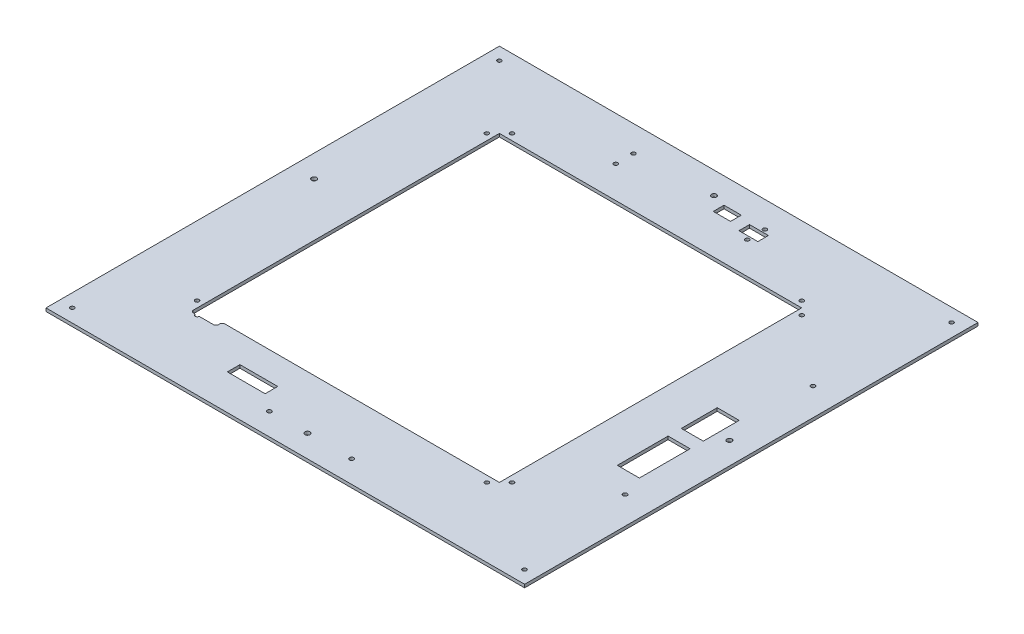
SolidWorks part; units mm, degrees
ref_plane "Front" through (0, 0, 0) normal (0, 0, 1) x (1, 0, 0)
ref_plane "Top" through (0, 0, 0) normal (0, 1, 0) x (1, 0, 0)
ref_plane "Right" through (0, 0, 0) normal (1, 0, 0) x (0, 0, -1)
sketch "Sketch1" plane through (0, 0, 0) normal (0, 1, 0) x (1, 0, 0)
  line L0 (-55, 0) -> (55, 0) construction
  line L1 (-242.5515, 228.6) -> (240.0485, 228.6)
  line L2 (-242.5515, 228.6) -> (-242.5515, -228.6)
  line L3 (-242.5515, -228.6) -> (240.0485, -228.6)
  line L4 (240.0485, 228.6) -> (240.0485, -228.6)
  line L5 (-242.5515, 228.6) -> (240.0485, -228.6) construction
  line L6 (-242.5515, -228.6) -> (240.0485, 228.6) construction
  line L7 (-166.3515, 152.4) -> (138.4485, 152.4)
  line L8 (-166.3515, 152.4) -> (-166.3515, -152.4)
  line L9 (-166.3515, -152.4) -> (138.4485, -152.4)
  line L10 (138.4485, 152.4) -> (138.4485, -152.4)
  line L11 (-166.3515, 152.4) -> (138.4485, -152.4) construction
  line L12 (-166.3515, -152.4) -> (138.4485, 152.4) construction
  line L13 (-160.0015, 146.05) -> (132.0985, 146.05)
  line L14 (-160.0015, 146.05) -> (-160.0015, -146.05)
  line L15 (-160.0015, -146.05) -> (132.0985, -146.05)
  line L16 (132.0985, 146.05) -> (132.0985, -146.05)
  line L17 (-160.0015, 146.05) -> (132.0985, -146.05) construction
  line L18 (-160.0015, -146.05) -> (132.0985, 146.05) construction
  line L19 (-166.3515, -152.4) -> (-140.9515, -152.4)
  line L20 (-166.3515, -152.4) -> (-166.3515, -158.75)
  line L21 (-166.3515, -158.75) -> (-140.9515, -158.75)
  line L22 (-140.9515, -152.4) -> (-140.9515, -158.75)
  line L23 (-242.5515, 0) -> (240.0485, 0) construction
  line L24 (58.4385, 188.214) -> (39.3885, 188.214)
  line L25 (58.4385, 188.214) -> (58.4385, 198.882)
  line L26 (58.4385, 198.882) -> (39.3885, 198.882)
  line L27 (39.3885, 188.214) -> (39.3885, 198.882)
  line L28 (182.9854, -26.8512) -> (205.1825, -26.8512)
  line L29 (182.9854, -26.8512) -> (182.9854, -78.0068)
  line L30 (182.9854, -78.0068) -> (205.1825, -78.0068)
  line L31 (205.1825, -26.8512) -> (205.1825, -78.0068)
  line L32 (182.9854, -13.5376) -> (205.1825, -13.5376)
  line L33 (182.9854, -13.5376) -> (182.9854, 22.6879)
  line L34 (182.9854, 22.6879) -> (205.1825, 22.6879)
  line L35 (205.1825, -13.5376) -> (205.1825, 22.6879)
  line L40 (27.0379, 202.954) -> (9.5991, 202.954)
  line L41 (27.0379, 202.954) -> (27.0379, 192.0704)
  line L42 (27.0379, 192.0704) -> (9.5991, 192.0704)
  line L43 (9.5991, 202.954) -> (9.5991, 192.0704)
  line L44 (-95.2315, -180.3456) -> (-57.1315, -180.3456)
  line L45 (-95.2315, -180.3456) -> (-95.2315, -193.0456)
  line L46 (-95.2315, -193.0456) -> (-57.1315, -193.0456)
  line L47 (-57.1315, -180.3456) -> (-57.1315, -193.0456)
  circle A0 centre (51.3519, 202.311) radius 2
  circle A1 centre (51.3519, 184.531) radius 2
  circle A2 centre (-81.1091, 202.311) radius 2
  circle A3 centre (-81.1091, 184.531) radius 2
  circle A4 centre (212.3904, -99.5798) radius 2.0955
  circle A5 centre (212.3904, 89.828) radius 2.0955
  circle A6 centre (-39.6436, -206.2861) radius 2.1
  circle A7 centre (43.3382, -206.2861) radius 2.1
  circle A8 centre (-172.7335, 146.082) radius 2
  circle A9 centre (-160.0335, 158.782) radius 2
  circle A12 centre (-160.0335, -158.782) radius 2
  circle A13 centre (-172.7335, -146.082) radius 2
  circle A14 centre (132.1305, 158.782) radius 2
  circle A15 centre (144.8305, 146.082) radius 2
  circle A16 centre (144.8305, -146.082) radius 2
  circle A17 centre (132.1305, -158.782) radius 2
  circle A18 centre (-229.8327, 215.8812) radius 2
  circle A19 centre (226.7201, 215.2716) radius 2
  circle A20 centre (-229.3755, -215.2716) radius 2
  circle A21 centre (227.2281, -215.9066) radius 2
  circle A22 centre (-220.0871, 19.264) radius 2.54
  circle A23 centre (-1.2915, -206.2372) radius 2.54
  circle A24 centre (-3.8315, 206.2626) radius 2.54
  circle A25 centre (217.7111, 0.294) radius 2.54
  point P0 (-1.2515, 0)
  point P6 (-44.5662, -1.1741)
  point P11 (-84.1987, 3.6789)
  point P21 (-13.9515, 0)
  point P22 (-13.9515, 0)
  point P23 (-1.2515, 0)
  dimension "D15" = 4
  dimension "D16" = 4
  dimension "D17" = 26.289
  dimension "D18" = 17.78
  dimension "D19" = 188.6966
  dimension "D20" = 132.461
  dimension "D22" = 27.6581
  dimension "D23" = 4.191
  dimension "D24" = 129.0202
  dimension "D26" = 4.2
  dimension "D27" = 22.3139
  dimension "D28" = 202.9079
  dimension "D29" = 82.9818
  dimension "D33" = 69.818
  dimension "D34" = 82.518
  dimension "D35" = 4
  dimension "D36" = 69.818
  dimension "D37" = 82.518
  dimension "D38" = 4
  dimension "D39" = 107.918
  dimension "D40" = 69.818
  dimension "D41" = 95.218
  dimension "D42" = 82.518
  dimension "D43" = 95.218
  dimension "D44" = 82.518
  dimension "D45" = 69.818
  dimension "D46" = 107.918
  dimension "D47" = 4
  dimension "D48" = 4
  dimension "D49" = 4
  dimension "D50" = 4
  dimension "D51" = 12.7188
  dimension "D53" = 13.3284
  dimension "D54" = 13.3284
  dimension "D55" = 13.176
  dimension "D56" = 13.3284
  dimension "D57" = 4
  dimension "D58" = 4
  dimension "D59" = 4
  dimension "D60" = 12.8204
  dimension "D61" = 4
  dimension "D62" = 12.6934
  dimension "D63" = 22.4644
  dimension "D64" = 247.864
  dimension "D65" = 22.3628
  dimension "D66" = 241.26
  dimension "D67" = 5.08
  dimension "D68" = 5.08
  dimension "D69" = 5.08
  dimension "D70" = 22.3374
  dimension "D71" = 238.72
  dimension "D72" = 22.3374
  dimension "D73" = 228.306
  dimension "D74" = 5.08
  dimension "D1" = 457.2
  dimension "D2" = 482.6
  dimension "D3" = 304.8
  dimension "D4" = 304.8
  dimension "D5" = 76.2
  dimension "D6" = 292.1
  dimension "D7" = 146.05
  dimension "D8" = 228.6
  dimension "D9" = 25.4
  dimension "D10" = 6.35
  dimension "D11" = 10.668
  dimension "D12" = 181.61
  dimension "D13" = 19.05
  dimension "D14" = 29.718
  dimension "D21" = 17.78
  dimension "D25" = 189.4078
  dimension "D30" = 12.7
  dimension "D31" = 185.42
  dimension "D32" = 38.1
  dimension "D52" = 12.7188
extrude "Boss-Extrude1" add sketch "Sketch1" along normal blind 3.175 contours L4 L1 L2 L3 L7 L10 L9 L8 region at (-1.2515, 0, -221.9522)
fillet "Fillet1" radius 2.54 3 edges at (-140.9515, 1.5875, 158.75) (-166.3515, 1.5875, 158.75) (-140.9515, 1.5875, 152.4)
